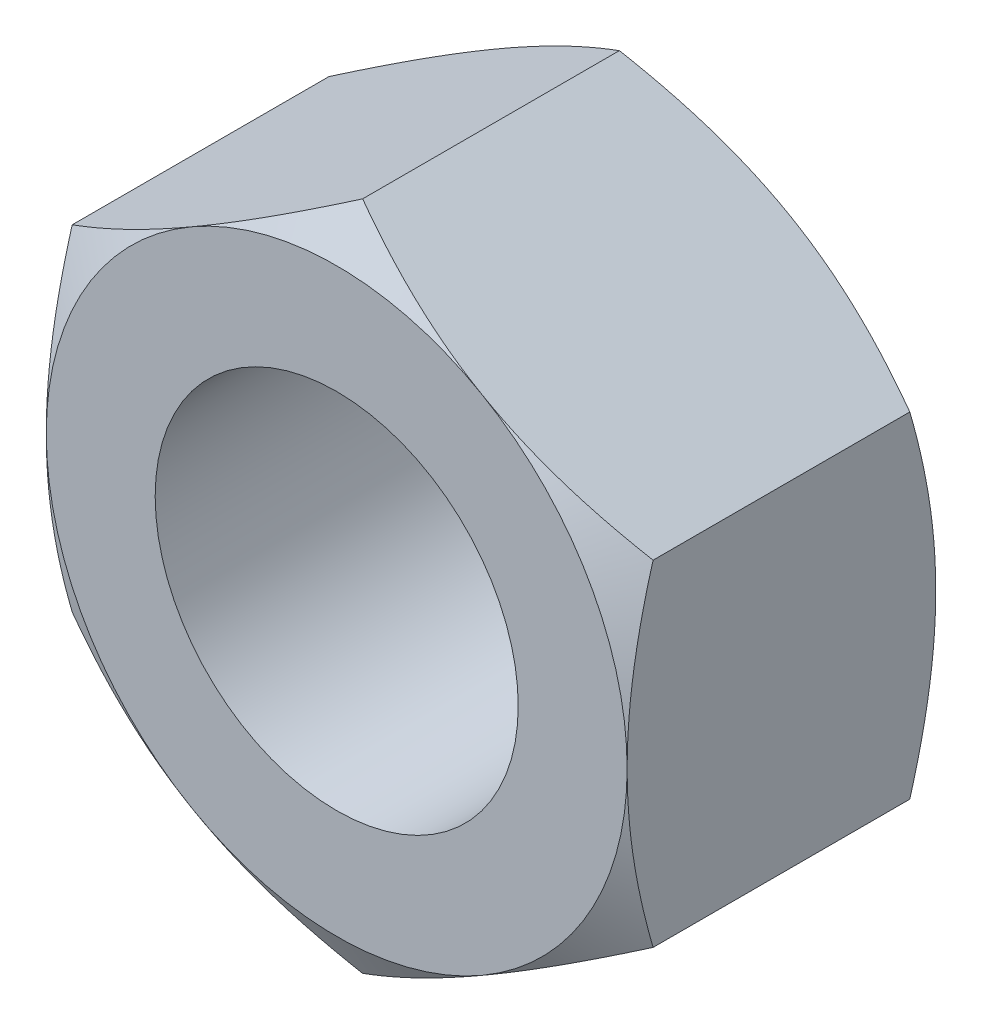
SolidWorks part; units mm, degrees
ref_plane "Front" through (0, 0, 0) normal (0, 0, 1) x (1, 0, 0)
ref_plane "Top" through (0, 0, 0) normal (0, 1, 0) x (1, 0, 0)
ref_plane "Right" through (0, 0, 0) normal (1, 0, 0) x (0, 0, -1)
sketch "Sketch1" plane through (0, 0, 0) normal (0, 0, 1) x (1, 0, 0)
  line L1 (-6.35, 3.6662) -> (-6.35, -3.6662)
  line L2 (-6.35, -3.6662) -> (0, -7.3323)
  line L3 (0, -7.3323) -> (6.35, -3.6662)
  line L4 (6.35, -3.6662) -> (6.35, 3.6662)
  line L5 (6.35, 3.6662) -> (0, 7.3323)
  line L6 (0, 7.3323) -> (-6.35, 3.6662)
  circle A0 centre (0, 0) radius 6.35 construction
  circle A1 centre (0, 0) radius 3.9688
  point P10 (0, 3.9688)
  dimension "hex" = 12.7
  dimension "dia" = 7.9375
extrude "Extrude1" add sketch "Sketch1" along normal mid plane 6.7469
sketch "Sketch4" plane through (0, 0, -3.3734) normal (0, 0, -1) x (-1, 0, 0)
  circle A0 centre (0, 0) radius 3.9688 construction
  circle A1 centre (0, 0) radius 3.9688
curve "Helix/Spiral3" [suppressed] pitch 1.4111 height 8.0962 turns 5.7375
sketch "Sketch3" plane through (0, 0, 0) normal (1, 0, 0) x (0, 0, -1)
  line L0 (3.3734, 3.9688) -> (4.6082, 3.9688)
  line L1 (4.6082, 3.9688) -> (4.079, 3.0522)
  line L2 (4.079, 3.0522) -> (3.9026, 3.0522)
  line L3 (3.9026, 3.0522) -> (3.3734, 3.9688)
  line L4 (3.638, 3.5105) -> (4.3436, 3.5105) construction
  dimension "D1" = 60
  dimension "D2" = 0.7056
  dimension "D3" = 0.1764
sweep "Sweep1" [suppressed] add profiles "Sketch3" path "Helix/Spiral3"
sketch "Sketch6" [suppressed] plane through (0, 0, 0) normal (1, 0, 0) x (0, 0, -1)
  line L0 (-3.7262, 4.3215) -> (-3.0207, 3.616)
  line L1 (-3.0207, 3.616) -> (-3.0207, 0) construction
  line L2 (3.9291, 0) -> (-3.9291, 0) construction
  line L3 (-3.0207, 0) -> (-4.7235, 0)
  line L4 (-4.7235, 0) -> (-4.7235, 4.3215)
  line L5 (-4.7235, 4.3215) -> (-3.7262, 4.3215)
  line L6 (-3.0207, 3.616) -> (0.5953, 0)
  line L7 (0.5953, 0) -> (-3.0207, 0)
  line L8 (-3.3734, -3.6662) -> (-3.3734, 3.6662) construction
  point P2 (-3.3734, 3.9688)
  dimension "D2" = 0.7056
  dimension "D1" = 45
revolve "Cut-Revolve1" [suppressed] cut sketch "Sketch6" angle 360 about L3
sketch "Sketch7" plane through (0, 0, 3.3734) normal (0, 0, 1) x (1, 0, 0)
  circle A0 centre (0, 0) radius 6.35 construction
  circle A1 centre (0, 0) radius 6.35
extrude "Extrude2" cut sketch "Sketch7" against normal blind 25.4 draft 60 flip side to cut
mirror "Mirror1" about plane through (0, 0, 0) normal (0, 0, 1) of "Extrude2", "Cut-Revolve1"
sketch "Sketch8" [suppressed] plane through (0, 0, 3.3734) normal (0, 0, 1) x (1, 0, 0)
  line L0 (-2.8063, 2.8063) -> (0, 0) construction
  line L1 (0, -3.9291) -> (0, 3.9291) construction
  circle A0 centre (0, 0) radius 3.9688 construction
  point P0 (-2.8063, 2.8063)
  dimension "D1" = 45
equation "\"D3@Helix/Spiral3\" = \"length@Extrude1\" * 1.2"
equation "\"D2@Sketch3\" = \"D4@Helix/Spiral3\" * .5"
equation "\"D3@Sketch3\" = \"D4@Helix/Spiral3\" * .125"
equation "\"D2@Sketch6\" = \"D4@Helix/Spiral3\" * .5"
